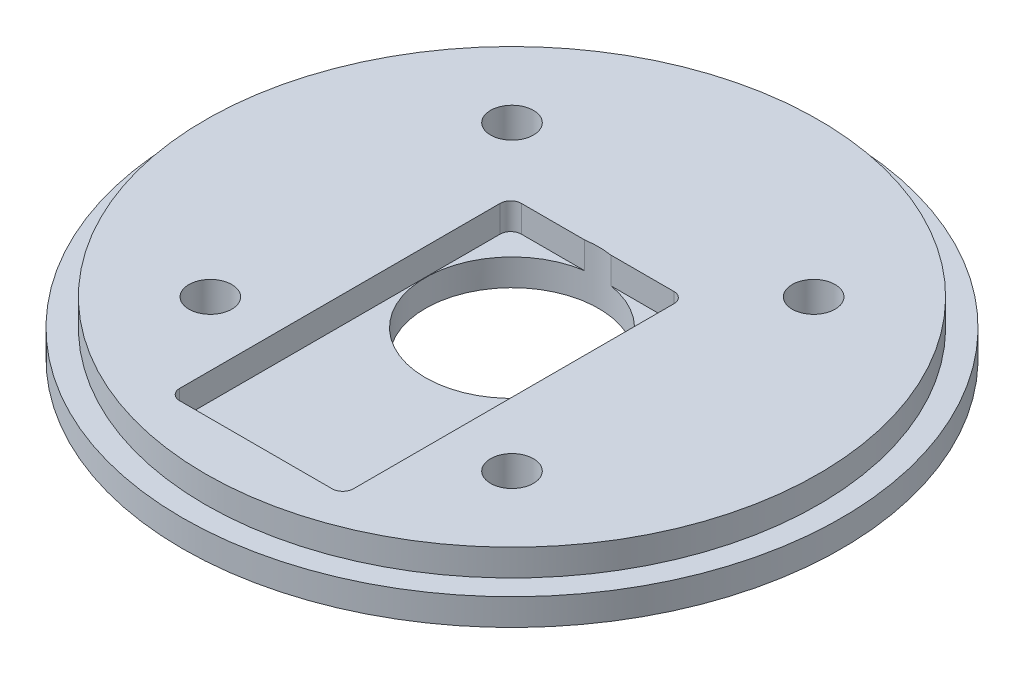
SolidWorks part; units mm, degrees
ref_plane "Front Plane" through (0, 0, 0) normal (0, 0, 1) x (1, 0, 0)
ref_plane "Top Plane" through (0, 0, 0) normal (0, 1, 0) x (1, 0, 0)
ref_plane "Right Plane" through (0, 0, 0) normal (1, 0, 0) x (0, 0, -1)
sketch "Sketch2" plane through (0, 0, 0) normal (0, 1, 0) x (1, 0, 0)
  circle A0 centre (0, 0) radius 39.243
  dimension "D1" = 78.486
extrude "Boss-Extrude1" add sketch "Sketch2" along normal blind 6.35
sketch "Sketch4" plane through (0, 6.35, 0) normal (0, 1, 0) x (1, 0, 0)
  circle A0 centre (0, 0) radius 36.5125
  circle A1 centre (0, 0) radius 39.243 construction
  circle A2 centre (0, 0) radius 39.243
  dimension "D1" = 73.025
extrude "Cut-Extrude1" cut sketch "Sketch4" against normal blind 3.175
sketch "Sketch5" plane through (0, 6.35, 0) normal (0, 1, 0) x (1, 0, 0)
  line L0 (17.9605, 17.9605) -> (-17.9605, -17.9605) construction
  line L1 (-17.9605, 17.9605) -> (17.9605, -17.9605) construction
  line L2 (-1000, 0) -> (49000, 0) construction
  point P1 (-17.9605, -17.9605)
  point P2 (17.9605, 17.9605)
  point P5 (17.9605, -17.9605)
  point P6 (-17.9605, 17.9605)
  dimension "D1" = 50.8
  dimension "D2" = 45
hole_wizard "Tap Drill for 1/4-20 Tap1" positions "Sketch5" profile "Sketch6" hole size "1/4-20" standard "ANSI Inch" end condition through all
sketch "Sketch6" plane through (-17.9605, 6.35, -17.9605) normal (1, 0, 0) x (0, 0, 1)
  line L0 (0, 0) -> (0, 6.35)
  line L1 (0, 6.35) -> (2.5527, 6.35)
  line L2 (2.5527, 6.35) -> (2.5527, 0)
  line L5 (2.5527, 0) -> (0, 0)
  line L11 (0, -6.35) -> (0, 107.95) construction
  dimension "Thru Hole Dia." = 5.1054
  dimension "Thru Hole Depth" = 6.35
sketch "Sketch7" plane through (0, 6.35, 0) normal (0, 1, 0) x (1, 0, 0)
  point P0 (0, 0)
hole_wizard "13/16 (0.8125) Diameter Hole1" positions "Sketch7" profile "Sketch8" hole size "13/16" standard "ANSI Inch" end condition through all
sketch "Sketch8" plane through (0, 6.35, 0) normal (1, 0, 0) x (0, 0, 1)
  line L0 (0, 0) -> (0, 6.35)
  line L1 (0, 6.35) -> (10.3187, 6.35)
  line L2 (10.3187, 6.35) -> (10.3187, 0)
  line L5 (10.3187, 0) -> (0, 0)
  line L11 (0, -6.35) -> (0, 107.95) construction
  dimension "Thru Hole Dia." = 20.6375
  dimension "Thru Hole Depth" = 6.35
sketch "Sketch9" plane through (0, 0, 0) normal (0, -1, 0) x (1, 0, 0)
  circle A0 centre (-17.9605, -17.9605) radius 2.5527 construction
  circle A1 centre (17.9605, -17.9605) radius 2.5527 construction
  circle A2 centre (17.9605, 17.9605) radius 2.5527 construction
  circle A3 centre (-17.9605, 17.9605) radius 2.5527 construction
  circle A4 centre (-17.9605, -17.9605) radius 2.5527 construction
  circle A5 centre (17.9605, -17.9605) radius 2.5527 construction
  circle A6 centre (17.9605, 17.9605) radius 2.5527 construction
  circle A7 centre (-17.9605, 17.9605) radius 2.5527 construction
  circle A8 centre (-17.9605, 17.9605) radius 6.35
  circle A9 centre (17.9605, 17.9605) radius 6.35
  circle A10 centre (17.9605, -17.9605) radius 6.35
  circle A11 centre (-17.9605, -17.9605) radius 6.35
  point P13 (-17.9605, 17.9605)
  point P14 (17.9605, 17.9605)
  point P15 (17.9605, -17.9605)
  point P16 (-17.9605, -17.9605)
  dimension "D1" = 12.7
extrude "Cut-Extrude2" cut sketch "Sketch9" against normal blind 1.5875
sketch "Sketch11" plane through (0, 6.35, 0) normal (0, 1, 0) x (1, 0, 0)
  line L1 (-10.35, 10.2) -> (10.35, 10.2)
  line L2 (-10.35, 10.2) -> (-10.35, -30.5)
  line L3 (-10.35, -30.5) -> (10.35, -30.5)
  line L4 (10.35, 10.2) -> (10.35, -30.5)
  line L5 (-10.35, 10.2) -> (10.35, -30.5) construction
  line L6 (-10.35, -30.5) -> (10.35, 10.2) construction
  point P0 (0, 0)
  point P1 (0, -10.15)
  dimension "D1" = 10.2
  dimension "D2" = 20.7
  dimension "D3" = 40.7
extrude "Cut-Extrude3" cut sketch "Sketch11" against normal blind 3.175
fillet "Fillet1" radius 1.27 4 edges at (-10.35, 4.7625, -10.2) (-10.35, 4.7625, 30.5) (10.35, 4.7625, 30.5) (10.35, 4.7625, -10.2)
equation "\"AIRFRAME_OD\"= 3.091in"
equation "\"AIRFRAME_ID\"= 3.00in"
equation "\"FLAT_T\"= 0.125in"
equation "\"NOSE_EXP_L\"= 3.5in"
equation "\"NOSE_SHOULDER_L\"= 5in"
equation "\"MAIN_L\"= 30in"
equation "\"RECO_COUP_L\"= 6in"
equation "\"RECO_SWITCH_L\"= 1.5in"
equation "\"DROGUE_L\"= 14in"
equation "\"ATS_FORE_COUP_L\"= 4in"
equation "\"ATS_AFT_COUP_L\"= 4in"
equation "\"LOWER_L\"= 16in"
equation "\"FIN_N\"= 4"
equation "\"CR_AFT_X\"= 0.5in"
equation "\"CR_FORE_X\"= 6in"
equation "\"D1@Boss-Extrude1\"=2*\"FLAT_T\""
equation "\"COUPLER_OD\"= 2.998in"
equation "\"COUPLER_ID\"= 2.875in"
equation "\"RECO_ROD_X\"= 1.5in"
equation "\"ATS_ROD_X\"= 2in"
equation "\"FIN_ROOT\"= 5in"
equation "\"FIN_X\"= 0.75in"
equation "\"MOTOR_OD\"= 2.25in"
equation "\"MOTOR_ID\"= 2.126in"
equation "\"MOTOR_L\"= 8in"
equation "\"MOTOR_LOWER_X\"= 0.5in"
equation "\"D1@Sketch4\"=\"COUPLER_ID\""
equation "\"D1@Cut-Extrude1\"=\"FLAT_T\""
equation "\"D1@Cut-Extrude3\"=\"FLAT_T\""
